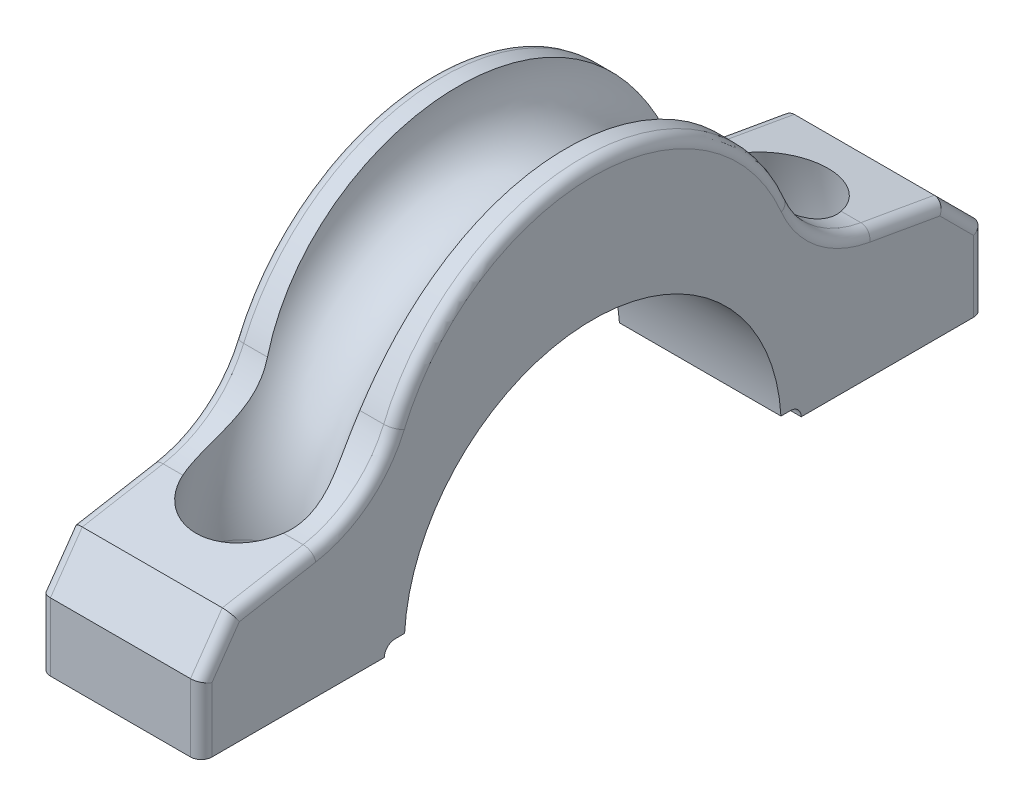
SolidWorks part; units mm, degrees
ref_plane "Front Plane" through (0, 0, 0) normal (0, 0, 1) x (1, 0, 0)
ref_plane "Top Plane" through (0, 0, 0) normal (0, 1, 0) x (1, 0, 0)
ref_plane "Right Plane" through (0, 0, 0) normal (1, 0, 0) x (0, 0, -1)
sketch "Sketch1" plane through (0, 0, 0) normal (1, 0, 0) x (0, 0, -1)
  line L0 (-72.7077, 0) -> (-55.7077, 0)
  line L1 (0, 0) -> (0, 10)
  line L2 (0, 10) -> (-16.5684, 12.9215)
  line L3 (-36.3538, 17.5) -> (-36.3538, 45.3769) construction
  line L4 (-72.7077, 0) -> (-72.7077, 10)
  line L5 (-72.7077, 10) -> (-56.1393, 12.9215)
  line L6 (-17, 0) -> (-17, 1)
  line L7 (-17, 1) -> (-18.8824, 1)
  line L8 (-55.7077, 0) -> (-55.7077, 1)
  line L9 (-55.7077, 1) -> (-53.8253, 1)
  line L10 (-17, 0) -> (0, 0)
  arc A0 (-56.1393, 12.9215) -> (-16.5684, 12.9215) centre (-36.3538, 10) cw
  arc A1 (-18.8824, 1) -> (-53.8253, 1) centre (-36.3538, 0) ccw
  point P10 (-36.3538, 30)
  dimension "D1" = 20
  dimension "D5" = 30
  dimension "D7" = 17.5
  dimension "D2" = 72.7077
  dimension "D3" = 10
  dimension "D4" = 80
  dimension "D6" = 1
  dimension "D8" = 17
extrude "Boss-Extrude1" add sketch "Sketch1" along normal blind 15
fillet "Fillet1" radius 10 2 edges at (7.5, 12.9215, 16.5684) (7.5, 12.9215, 56.1393)
chamfer "Chamfer1" distance 3 angle 45 2 edges at (7.5, 10, 0) (7.5, 10, 72.7077) first distance on face at (7.5, 5, 0) first distance on face at (7.5, 10.9224, 67.4762)
fillet "Fillet2" radius 1 9 edges at (15, 11.2436, 7.0526) (15, 13.8702, 14.9557) (15, 3.5, 0) (15, 8.8211, 1.8211) (15, 30, 36.3538) (15, 13.8702, 57.752) (15, 11.1829, 65.999) (15, 8.4113, 71.2305) (15, 3.1508, 72.7077)
fillet "Fillet3" radius 1 9 edges at (0, 11.1829, 65.999) (0, 13.8702, 57.752) (0, 30, 36.3538) (0, 13.8702, 14.9557) (0, 3.1508, 72.7077) (0, 8.4113, 71.2305) (0, 11.2436, 7.0526) (0, 8.8211, 1.8211) (0, 3.5, 0)
ref_plane "Plane1" through (7.5, 0, 0) normal (1, 0, 0) x (0, 0, -1)
sketch "Sketch2" plane through (7.5, 0, 0) normal (1, 0, 0) x (0, 0, -1)
  line L0 (-36.3538, 0) -> (-36.3538, 38.9315) construction
  line L1 (-71.7077, 0) -> (-55.7077, 0) construction
  line L2 (-11.3538, -10) -> (-11.3538, 5)
  line L3 (-61.3538, -10) -> (-61.3538, 5)
  arc A0 (-11.3538, 5) -> (-61.3538, 5) centre (-36.3538, 5) ccw
  dimension "D1" = 50
  dimension "D2" = 15
  dimension "D3" = 10
ref_plane "Plane4" through (0, 0, 71.7077) normal (0, 0, -1) x (-1, 0, 0)
ref_plane "Plane5" through (0, -10, 0) normal (0, -1, 0) x (-1, 0, 0)
sketch "Sketch5" plane through (0, -10, 0) normal (0, -1, 0) x (-1, 0, 0)
  circle A0 centre (-7.5, -11.3538) radius 5
  dimension "D1" = 10
sweep "augu cut" cut profiles "Sketch5" path "Sketch2"
fillet "Fillet6" radius 1 2 edges at (7.5, 1, 55.7077) (7.5, 1, 17)
